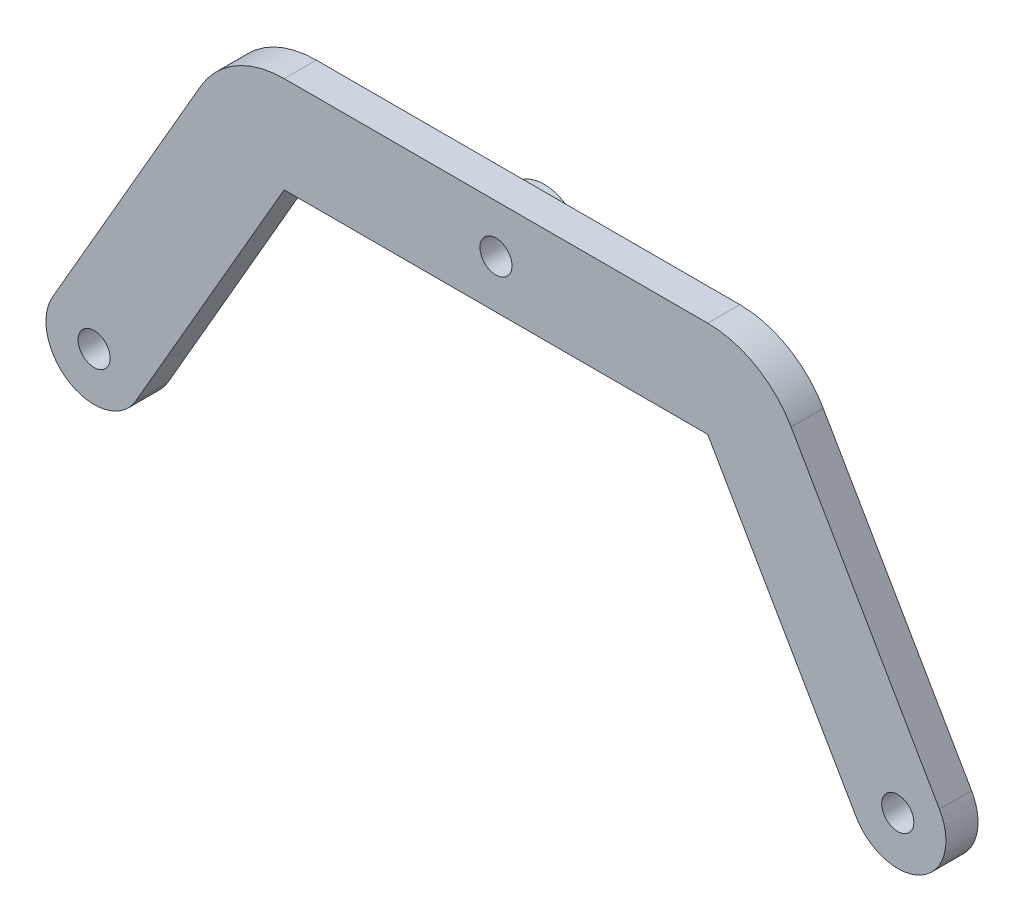
SolidWorks part; units mm, degrees
ref_plane "Front Plane" through (0, 0, 0) normal (0, 0, 1) x (1, 0, 0)
ref_plane "Top Plane" through (0, 0, 0) normal (0, 1, 0) x (1, 0, 0)
ref_plane "Right Plane" through (0, 0, 0) normal (1, 0, 0) x (0, 0, -1)
sketch "Sketch1" plane through (0, 0, 0) normal (0, 0, 1) x (1, 0, 0)
  line L0 (0, -15) -> (0, 15) construction
  line L1 (65.9559, 15) -> (-65.9559, 15)
  line L2 (65.9559, -15) -> (-65.9559, -15)
  line L3 (-65.9559, -15) -> (-112.1545, -95.0183)
  line L5 (-138.1353, -80.0183) -> (-91.9367, 0)
  line L6 (138.1353, -80.0183) -> (91.9367, 0)
  line L8 (65.9559, -15) -> (112.1545, -95.0183)
  arc A1 (-91.9367, 0) -> (-65.9559, 15) centre (-65.9559, -15) cw
  arc A2 (91.9367, 0) -> (65.9559, 15) centre (65.9559, -15) ccw
  circle A3 centre (-125.1449, -87.5183) radius 15 construction
  arc A5 (-138.1353, -80.0183) -> (-112.1545, -95.0183) centre (-125.1449, -87.5183) ccw
  arc A6 (112.1545, -95.0183) -> (138.1353, -80.0183) centre (125.1449, -87.5183) ccw
  point P4 (0, 0)
  point P6 (0, 15)
  point P10 (0, -15)
  point P11 (0, 0)
  point P21 (0, 0)
  point P22 (118.2893, -77.8202)
  point P24 (0, 0)
  point P25 (0, 0)
  dimension "D1" = 30
  dimension "D3" = 120
extrude "Boss-Extrude1" add sketch "Sketch1" along normal blind 10
sketch "Sketch2" plane through (0, 0, 10) normal (0, 0, 1) x (1, 0, 0)
  circle A0 centre (0, 0) radius 5
  circle A1 centre (-125.1449, -87.5183) radius 5
  circle A2 centre (125.1449, -87.5183) radius 5
extrude "Cut-Extrude1" cut sketch "Sketch2" against normal up to surface (10 mm away) up to face at (0, -36.9092, 0)
sketch "Sketch3" plane through (0, 0, 0) normal (0, 0, -1) x (-1, 0, 0)
  circle A0 centre (0, 0) radius 12
extrude "Boss-Extrude2" add sketch "Sketch3" along normal blind 5
